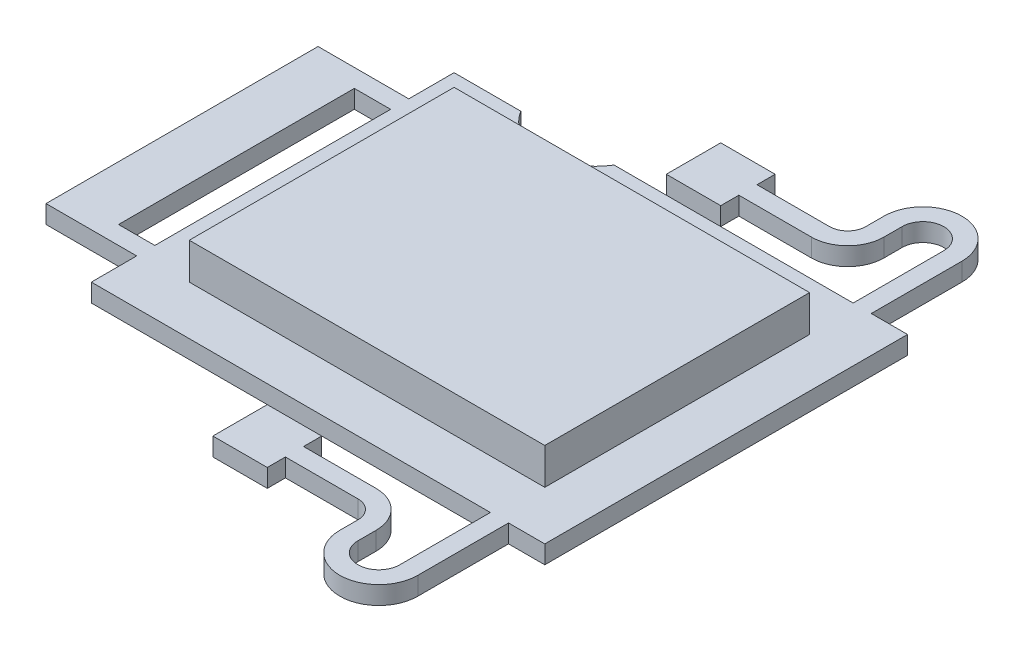
SolidWorks part; units mm, degrees
material "PLA"
ref_plane "Спереди" through (0, 0, 0) normal (0, 0, 1) x (1, 0, 0)
ref_plane "Сверху" through (0, 0, 0) normal (0, 1, 0) x (1, 0, 0)
ref_plane "Справа" through (0, 0, 0) normal (1, 0, 0) x (0, 0, -1)
sketch "Эскиз1" plane through (0, 0, 0) normal (0, 1, 0) x (1, 0, 0)
  line L1 (12.5, 10) -> (-12.5, 10)
  line L2 (12.5, 10) -> (12.5, -10)
  line L3 (12.5, -10) -> (-12.5, -10)
  line L4 (-12.5, 10) -> (-12.5, -10)
  line L5 (12.5, 10) -> (-12.5, -10) construction
  line L6 (12.5, -10) -> (-12.5, 10) construction
  point P0 (0, 0)
  dimension "D1" = 25
  dimension "D2" = 20
extrude "Бобышка-Вытянуть1" add sketch "Эскиз1" along normal blind 1
sketch "Эскиз3" plane through (0, 0, 0) normal (0, 1, 0) x (1, 0, 0)
  line L0 (0, 0) -> (-50000, 0) construction
  line L1 (-12.5, 10) -> (-12.5, -10) construction
  line L6 (-14.5, 7.5) -> (-17.5, 7.5)
  line L7 (-14.5, 6.5) -> (-14.5, -6.5)
  line L8 (-14.5, -7.5) -> (-17.5, -7.5)
  line L9 (-17.5, 7.5) -> (-17.5, -7.5)
  line L10 (-14.5, 7.5) -> (-17.5, -7.5) construction
  line L11 (-14.5, -7.5) -> (-17.5, 7.5) construction
  line L12 (-14.5, 7.5) -> (-12.5, 7.5)
  line L13 (-12.5, 7.5) -> (-12.5, 6.5)
  line L14 (-12.5, 6.5) -> (-14.5, 6.5)
  line L15 (-12.5, -6.5) -> (-14.5, -6.5)
  line L16 (-12.5, -7.5) -> (-12.5, -6.5)
  line L17 (-14.5, -7.5) -> (-12.5, -7.5)
  line L18 (-14.5, 7.5) -> (-14.5, 6.5) construction
  point P3 (-16, 0)
  dimension "D1" = 3
  dimension "D2" = 15
  dimension "D3" = 2
  dimension "D4" = 1
extrude "Бобышка-Вытянуть2" add sketch "Эскиз3" along normal blind 1
sketch "Эскиз4" plane through (0, 0, 0) normal (0, 1, 0) x (1, 0, 0)
  line L0 (0, 0) -> (50000, 0) construction
  line L1 (9.5, 10) -> (9.5, 15)
  line L2 (12.5, 10) -> (-12.5, 10) construction
  line L3 (7.2, 15) -> (7.2, 14)
  line L4 (5.2, 12) -> (1.2, 12)
  line L5 (10.5, 10) -> (10.5, 15)
  line L6 (6.2, 15) -> (6.2, 14)
  line L7 (5.2, 13) -> (1.2, 13)
  line L8 (10.5, 10) -> (9.5, 10)
  line L9 (1.2, 13) -> (1.2, 12) construction
  line L10 (-1.8, 11) -> (1.2, 11)
  line L11 (-1.8, 11) -> (-1.8, 14)
  line L12 (1.2, 11) -> (1.2, 12)
  line L13 (-1.8, 14) -> (1.2, 14)
  line L14 (-1.8, 11) -> (1.2, 14) construction
  line L15 (1.2, 11) -> (-1.8, 14) construction
  line L16 (1.2, 13) -> (1.2, 14)
  line L17 (1.2, 12.5) -> (-0.3, 12.5) construction
  line L18 (12.5, -10) -> (12.5, 10) construction
  line L19 (-1.8, -11) -> (-1.8, -14)
  line L20 (-1.8, -14) -> (1.2, -14)
  line L21 (1.2, -13) -> (1.2, -14)
  line L22 (5.2, -13) -> (1.2, -13)
  line L23 (6.2, -15) -> (6.2, -14)
  line L24 (10.5, -10) -> (10.5, -15)
  line L25 (10.5, -10) -> (9.5, -10)
  line L26 (9.5, -10) -> (9.5, -15)
  line L27 (7.2, -15) -> (7.2, -14)
  line L28 (5.2, -12) -> (1.2, -12)
  line L29 (1.2, -11) -> (1.2, -12)
  line L30 (-1.8, -11) -> (1.2, -11)
  arc A0 (9.5, 15) -> (7.2, 15) centre (8.35, 15) ccw
  arc A1 (7.2, 14) -> (5.2, 12) centre (5.2, 14) cw
  arc A2 (10.5, 15) -> (6.2, 15) centre (8.35, 15) ccw
  arc A3 (6.2, 14) -> (5.2, 13) centre (5.2, 14) cw
  arc A4 (6.2, -14) -> (5.2, -13) centre (5.2, -14) ccw
  arc A5 (10.5, -15) -> (6.2, -15) centre (8.35, -15) cw
  arc A6 (9.5, -15) -> (7.2, -15) centre (8.35, -15) cw
  arc A7 (7.2, -14) -> (5.2, -12) centre (5.2, -14) ccw
  point P22 (-0.3, 12.5)
  dimension "D4" = 2.15
  dimension "D5" = 2
  dimension "D1" = 1
  dimension "D2" = 3
  dimension "D3" = 3
  dimension "D6" = 1
  dimension "D7" = 4
  dimension "D8" = 5
  dimension "D9" = 2
extrude "Бобышка-Вытянуть3" add sketch "Эскиз4" along normal blind 1
sketch "Эскиз5" plane through (0, 1, 0) normal (0, 1, 0) x (1, 0, 0)
  line L1 (9.8, 7.3) -> (-9.8, 7.3)
  line L2 (9.8, 7.3) -> (9.8, -7.3)
  line L3 (9.8, -7.3) -> (-9.8, -7.3)
  line L4 (-9.8, 7.3) -> (-9.8, -7.3)
  line L5 (9.8, 7.3) -> (-9.8, -7.3) construction
  line L6 (9.8, -7.3) -> (-9.8, 7.3) construction
  point P0 (0, 0)
  point P6 (0, 0)
  point P9 (0, 0)
  dimension "D1" = 19.6
  dimension "D2" = 14.6
extrude "Бобышка-Вытянуть4" add sketch "Эскиз5" along normal blind 2
sketch "Эскиз6" plane through (0, 0, 0) normal (0, -1, 0) x (1, 0, 0)
  circle A0 centre (0, 0) radius 2
  dimension "D1" = 4
extrude "Вырез-Вытянуть2" cut sketch "Эскиз6" against normal offset from surface (2.8 mm away) 0.2 up to face at (0, 3, 0)
sketch "Эскиз7" plane through (0, 0, 0) normal (0, -1, 0) x (1, 0, 0)
  line L0 (9.5, -10) -> (-12.5, -10) construction
  line L1 (-12.5, -10) -> (-12.5, -7.5) construction
  circle A0 centre (-6.25, -11.55) radius 3
  dimension "D3" = 6
  dimension "D1" = 1.55
  dimension "D2" = 6.25
extrude "Вырез-Вытянуть3" cut sketch "Эскиз7" against normal up to surface (1 mm away) up to face at (2.4511, 1, 0)
